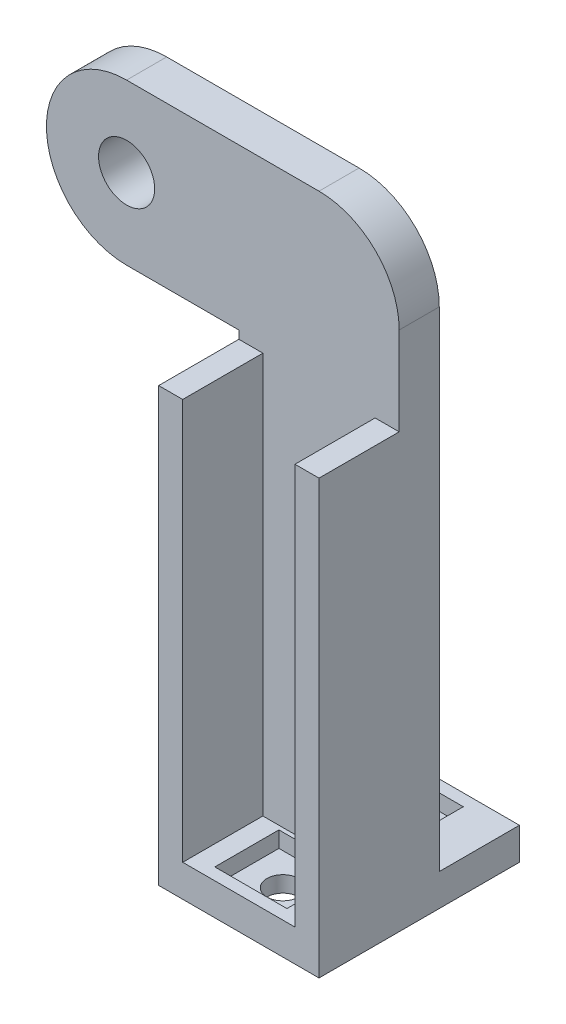
SolidWorks part; units mm, degrees
note: The reader was unsure of these and kept them because the rebuilt part matched: shared geometry of "Sketch1<3>".
ref_plane "Front Plane" through (0, 0, 0) normal (0, 0, 1) x (1, 0, 0)
ref_plane "Top Plane" through (0, 0, 0) normal (0, 1, 0) x (1, 0, 0)
ref_plane "Right Plane" through (0, 0, 0) normal (1, 0, 0) x (0, 0, -1)
sketch "Sketch1" plane through (0, 0, 0) normal (0, 0, 1) x (1, 0, 0)
  line L0 (0, 0) -> (0, 32.5) construction
  line L1 (5, 0) -> (5, 32.5)
  line L2 (-5, 0) -> (-5, 32.5)
  line L3 (-5, 0) -> (5, 0)
  line L4 (-5, 2) -> (5, 2)
  line L5 (0, 32.5) -> (-12, 32.5) construction
  line L6 (0, 37.5) -> (-12, 37.5)
  line L7 (0, 27.5) -> (-12, 27.5)
  circle A1 centre (0, 32.5) radius 5
  circle A2 centre (-12, 32.5) radius 5
  circle A3 centre (-12, 32.5) radius 1.75
  dimension "D3" = 10
  dimension "D4" = 10
  dimension "D7" = 3.5
  dimension "D5" = 32.5
  dimension "D6" = 2
  dimension "D8" = 12
  dimension "D1" = 5
  dimension "D2" = 5
  dimension "D9" = 5
  dimension "D10" = 5
extrude "AxleHolder" add sketch "Sketch1" along normal blind 2.5
extrude "Base" add sketch "Sketch1<3>" along normal blind 7.5 and the other way blind 5 contours L4 L2 L3 L1
sketch "Sketch1<3>" plane through (0, 0, 0) normal (0, 0, 1) x (1, 0, 0) same geometry as "Sketch1"
sketch "Sketch2" plane through (0, 2, 0) normal (0, 1, 0) x (1, 0, 0)
  line L0 (-5, -7.5) -> (5, -7.5) construction
  line L1 (-5, 5) -> (5, 5) construction
  line L2 (-5, -7.5) -> (5, -7.5) construction
  line L3 (-5, 5) -> (5, 5) construction
  line L4 (0, -7.5) -> (0, 5) construction
  circle A0 centre (0, 2.25) radius 1
  circle A1 centre (0, -4.75) radius 1
  point P10 (0, -1.25)
  dimension "D3" = 2
  dimension "D4" = 2
  dimension "D1" = 3.5
  dimension "D2" = 3.5
extrude "BoltHoles" cut sketch "Sketch2" against normal through all
sketch "Sketch3" plane through (0, 2, 0) normal (0, 1, 0) x (1, 0, 0)
  line L1 (-2.25, -6.75) -> (2.25, -6.75)
  line L2 (-2.25, -6.75) -> (-2.25, -2.75)
  line L3 (-2.25, -2.75) -> (2.25, -2.75)
  line L4 (2.25, -6.75) -> (2.25, -2.75)
  line L5 (0, -2.75) -> (0, -6.75) construction
  line L6 (-2.25, -4.75) -> (2.25, -4.75) construction
  line L7 (-2.25, 0.25) -> (2.25, 0.25)
  line L8 (-2.25, 0.25) -> (-2.25, 4.25)
  line L9 (-2.25, 4.25) -> (2.25, 4.25)
  line L10 (2.25, 0.25) -> (2.25, 4.25)
  line L11 (0, 4.25) -> (0, 0.25) construction
  line L12 (-2.25, 2.25) -> (2.25, 2.25) construction
  circle A0 centre (0, -4.75) radius 1 construction
  circle A1 centre (0, -4.75) radius 1 construction
  circle A2 centre (0, 2.25) radius 1 construction
  circle A3 centre (0, 2.25) radius 1 construction
  dimension "D2" = 4.5
  dimension "D3" = 4
  dimension "D4" = 4.5
extrude "NutSlots" cut sketch "Sketch3" against normal blind 1
sketch "Sketch4" plane through (0, 2, 0) normal (0, 1, 0) x (1, 0, 0)
  line L0 (-5, -2.5) -> (5, -2.5) construction
  line L1 (-5, -2.5) -> (5, -2.5) construction
  line L2 (-5, -7.5) -> (5, -7.5) construction
  line L3 (-5, -2.5) -> (-3.5, -2.5)
  line L4 (-5, -2.5) -> (-5, -7.5)
  line L5 (-5, -7.5) -> (-3.5, -7.5)
  line L6 (-3.5, -2.5) -> (-3.5, -7.5)
  dimension "D1" = 1.5
extrude "StiffenerRib" add sketch "Sketch4" along normal blind 25
mirror "StiffenerRib2" about plane through (0, 0, 0) normal (1, 0, 0) of "StiffenerRib"
equation "\"BoltD\"=2mm"
equation "\"BoltHatD\"=3.2mm"
equation "\"NutShortSide\"=4mm"
equation "\"NutLongSide\"=4.5mm"
equation "\"SmallScrewD\"=1.2mm"
equation "\"SmallScrewHatD\"=2mm"
equation "\"TubeOuterD\"=1.2mm"
equation "\"BasicPulleyD\"=15mm"
equation "\"GrooveDepth\"=0.7mm"
equation "\"Cable1D\"=0.4mm"
equation "\"Cable2D\"=0.3mm"
equation "\"BallBearingInnerD\"=2mm"
equation "\"BallBearingOuterD\"=4mm"
equation "\"BallBearingThickness\"=2mm"
equation "\"HumerusL\"=37.2mm"
equation "\"HumerusElbowSidePulleyD\"=10mm"
equation "\"RadiusL\"=68.1mm"
equation "\"Finger1L\"=120mm"
equation "\"Finger2L\"=100mm"
equation "\"Finger3L\"=80mm"
equation "\"ElbowExtendedAngle\"=140deg"
equation "\"ElbowFlexedAngle\"=38deg"
equation "\"D4@Sketch2\"=\"BoltD\""
equation "\"D3@Sketch2\"=\"BoltD\""
equation "\"D3@Sketch3\"=\"NutShortSide\""
equation "\"D4@Sketch3\"=\"NutLongSide\""
equation "\"D2@Sketch3\"=\"NutLongSide\""
equation "\"D1@Sketch3\"=\"NutShortSide\""
equation "\"TubeClipW\"=1.5mm"
equation "\"TubeClipH\"=1mm"
equation "\"TubeClipLock_SideL\"=1.6mm"
equation "\"TubeClipLock_W\"=0.7mm"
equation "\"BearingCapD\"=12mm"
equation "\"Digit5ExtendedAngle\"=80deg"
equation "\"Digit5FlexedAngle\"=24deg"
equation "\"Digit4ExtendedAngle\"=108deg"
equation "\"Digit4FlexedAngle\"=34deg"
equation "\"Digit3ExtendedAngle\"=145deg"
equation "\"Digit3FlexedAngle\"=44deg"
